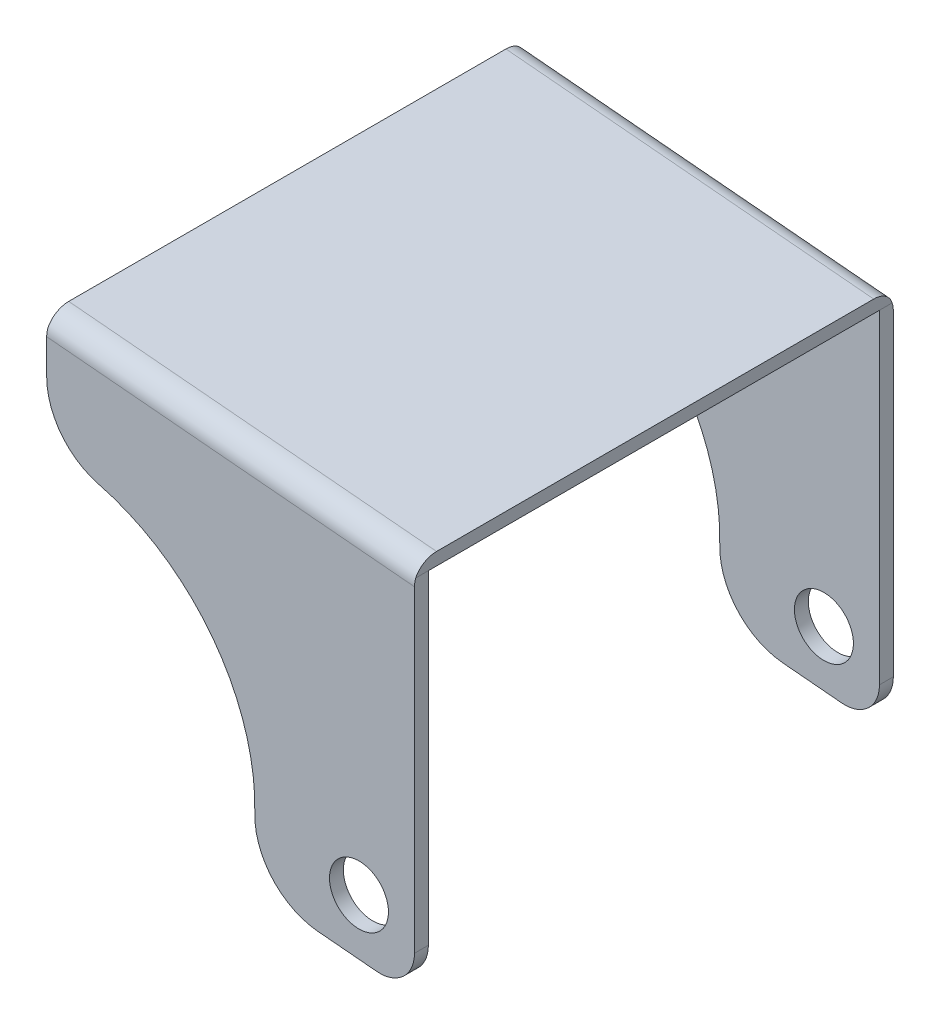
SolidWorks part; units mm, degrees
ref_plane "Front Plane" through (0, 0, 0) normal (0, 0, 1) x (1, 0, 0)
ref_plane "Top Plane" through (0, 0, 0) normal (0, 1, 0) x (1, 0, 0)
ref_plane "Right Plane" through (0, 0, 0) normal (1, 0, 0) x (0, 0, -1)
sketch "Sketch1" plane through (0, 0, 0) normal (0, 0, 1) x (1, 0, 0)
  line L0 (-27.5, 15.5152) -> (-27.5, 21.501)
  line L1 (-27.5, 21.501) -> (25.5, 16.7957)
  line L2 (25.5, 16.7957) -> (25.5, -35.4089)
  line L3 (25.5, -35.4089) -> (11.6032, -34.1751)
  arc A0 (2.4906, -23.9644) -> (-20, 5.8328) centre (-27.5, -23.2146) ccw
  arc A1 (-20, 5.8328) -> (-27.5, 15.5152) centre (-17.5, 15.5152) cw
  arc A2 (11.6032, -34.1751) -> (2.4906, -23.9644) centre (12.4875, -24.2143) cw
  point P11 (-27.5, 6.7854)
  point P14 (0.7843, -33.2146)
  dimension "D1" = 53
  dimension "D3" = 30
  dimension "D4" = 10
  dimension "D5" = 10
  dimension "D2" = 52
extrude "Boss-Extrude1" add sketch "Sketch1" along normal blind 2
fillet "Fillet1" radius 5 1 edges at (25.5, -35.4089, 1)
sketch "Sketch2" plane through (0, 0, 2) normal (0, 0, 1) x (1, 0, 0)
  line L0 (25.5, -29.9453) -> (25.5, 16.7957) construction
  line L1 (11.6032, -34.1751) -> (20.0578, -34.9257) construction
  circle A0 centre (17.5, -26.6672) radius 4.25
  dimension "D1" = 8.5
  dimension "D2" = 8
  dimension "D3" = 8
extrude "Cut-Extrude1" cut sketch "Sketch2" against normal blind 10
ref_plane "Plane1" through (0, 0, -32.5) normal (0, 0, -1) x (-1, 0, 0)
mirror "Mirror3" about plane through (0, 0, -32.5) normal (0, 0, -1) of bodies 102
sketch "Sketch3" plane through (1.6789, 18.9105, 0) normal (0.0884, 0.9961, 0) x (0.9961, -0.0884, 0)
  line L1 (-29.2937, 67) -> (23.9148, 67)
  line L2 (-29.2937, 67) -> (-29.2937, -2)
  line L3 (-29.2937, -2) -> (23.9148, -2)
  line L4 (23.9148, 67) -> (23.9148, -2)
extrude "Boss-Extrude2" add sketch "Sketch3" along normal blind 2
fillet "Fillet2" radius 3 2 edges at (-0.8231, 21.1405, 2) (-0.8231, 21.1405, -67)
